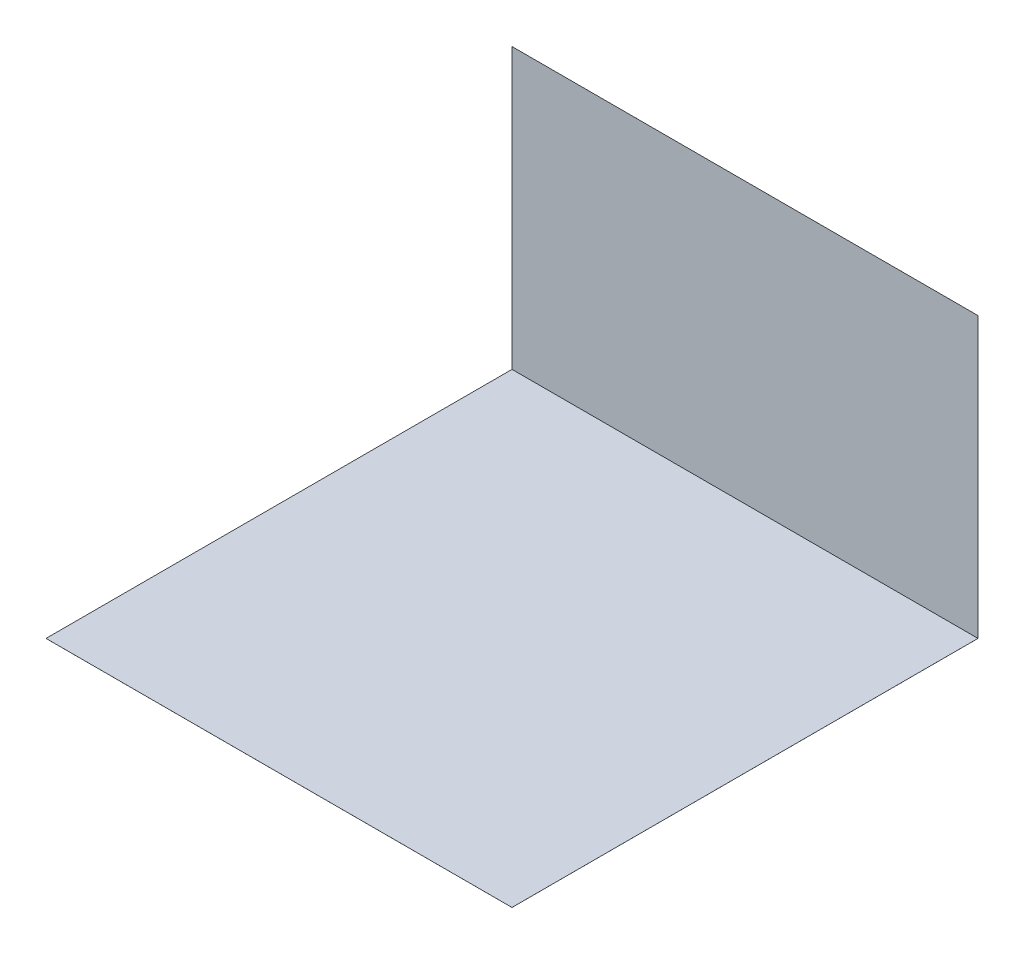
SolidWorks part; units mm, degrees
other "Floor"
ref_plane "Front Plane" through (0, 0, 0) normal (0, 0, 1) x (1, 0, 0)
ref_plane "Top Plane" through (0, 0, 0) normal (0, 1, 0) x (1, 0, 0)
ref_plane "Right Plane" through (0, 0, 0) normal (1, 0, 0) x (0, 0, -1)
sketch "Sketch2" plane through (0, 0, 0) normal (0, 1, 0) x (1, 0, 0)
  line L1 (-83.0204, 20.3435) -> (4916.9796, 20.3435)
  line L2 (-83.0204, 20.3435) -> (-83.0204, -4979.6565)
  line L3 (-83.0204, -4979.6565) -> (4916.9796, -4979.6565)
  line L4 (4916.9796, 20.3435) -> (4916.9796, -4979.6565)
  dimension "Width_Floor" = 5000
  dimension "Length_Floor" = 5000
extrude "Floor" add sketch "Sketch2" along normal blind 0.254
sketch "Sketch4" plane through (0, 0.254, 0) normal (0, 1, 0) x (1, 0, 0)
  line L0 (4916.9796, 20.3435) -> (-83.0204, 20.3435) construction
  line L1 (4916.9796, 20.3435) -> (-83.0204, 20.3435)
  dimension "wallBase" = 5000
extrude "Wall1" add sketch "Sketch4" along normal blind 3000 separate body thin thin type one direction wall 0.0254
sketch "Sketch5" [suppressed] plane through (0, 0, -20.3689) normal (0, 0, -1) x (-1, 0, 0)
  line L0 (-4916.9796, 0.254) -> (83.0204, 0.254) construction
  line L1 (-2.7195, 11.5038) -> (-2.6941, 11.5038)
  line L2 (-2.7195, 11.5038) -> (-2.7195, 11.4784)
  line L3 (-2.7195, 11.4784) -> (-2.6941, 11.4784)
  line L4 (-2.6941, 11.5038) -> (-2.6941, 11.4784)
  line L5 (83.0204, 3000.254) -> (83.0204, 0.254) construction
  dimension "Window1Display" = 0
  dimension "Window1Length" = 0
  dimension "Window1BottomOffset" = 0
  dimension "Window1RightOffset" = 0
extrude "WindowSlot1" [suppressed] cut sketch "Sketch5" against normal through all
sketch "Sketch7" [suppressed] plane through (0, 0, -20.3689) normal (0, 0, -1) x (-1, 0, 0)
  line L0 (-4916.9796, 0.254) -> (83.0204, 0.254) construction
  line L1 (33.338, 5.5809) -> (33.3634, 5.5809)
  line L2 (33.338, 5.5809) -> (33.338, 5.5555)
  line L3 (33.338, 5.5555) -> (33.3634, 5.5555)
  line L4 (33.3634, 5.5809) -> (33.3634, 5.5555)
  line L5 (83.0204, 3000.254) -> (83.0204, 0.254) construction
  dimension "Window2Display" = 0
  dimension "Window2Length" = 0
  dimension "Window2BottomOffset" = 0
  dimension "Window2RightOffset" = 0
extrude "WindowSlot2" [suppressed] cut sketch "Sketch7" against normal through all
sketch "Sketch8" [suppressed] plane through (0, 0, -20.3689) normal (0, 0, -1) x (-1, 0, 0)
  line L0 (-4916.9796, 0.254) -> (83.0204, 0.254) construction
  line L1 (69.0838, 8.4904) -> (69.1092, 8.4904)
  line L2 (69.0838, 8.4904) -> (69.0838, 8.465)
  line L3 (69.0838, 8.465) -> (69.1092, 8.465)
  line L4 (69.1092, 8.4904) -> (69.1092, 8.465)
  line L5 (83.0204, 3000.254) -> (83.0204, 0.254) construction
  dimension "Window3Display" = 0
  dimension "Window3Length" = 0
  dimension "Window3BottomOffset" = 0
  dimension "Window3RightOffset" = 0
extrude "WindowSlot3" [suppressed] cut sketch "Sketch8" against normal through all
sketch "Sketch9" [suppressed] plane through (0, 0, -20.3689) normal (0, 0, -1) x (-1, 0, 0)
  line L0 (-4916.9796, 0.254) -> (83.0204, 0.254) construction
  line L1 (-2.5117, 3.2948) -> (-2.4863, 3.2948)
  line L2 (-2.5117, 3.2948) -> (-2.5117, 3.2694)
  line L3 (-2.5117, 3.2694) -> (-2.4863, 3.2694)
  line L4 (-2.4863, 3.2948) -> (-2.4863, 3.2694)
  line L5 (83.0204, 3000.254) -> (83.0204, 0.254) construction
  dimension "Door1Display" = 0
  dimension "Door1length" = 0
  dimension "Door1BottomOffset" = 0
  dimension "Door1RightOffset" = 0
extrude "Door1" [suppressed] cut sketch "Sketch9" against normal through all
sketch "Sketch10" [suppressed] plane through (0, 0, -20.3689) normal (0, 0, -1) x (-1, 0, 0)
  line L0 (-4916.9796, 0.254) -> (83.0204, 0.254) construction
  line L1 (25.025, 5.0613) -> (25.0504, 5.0613)
  line L2 (25.025, 5.0613) -> (25.025, 5.0359)
  line L3 (25.025, 5.0359) -> (25.0504, 5.0359)
  line L4 (25.0504, 5.0613) -> (25.0504, 5.0359)
  line L5 (83.0204, 3000.254) -> (83.0204, 0.254) construction
  dimension "D1" = 0
  dimension "Door2Display" = 0
  dimension "Door2BottomOffset" = 0
  dimension "Door2RightOffset" = 0
extrude "Door2" [suppressed] cut sketch "Sketch10" against normal through all
